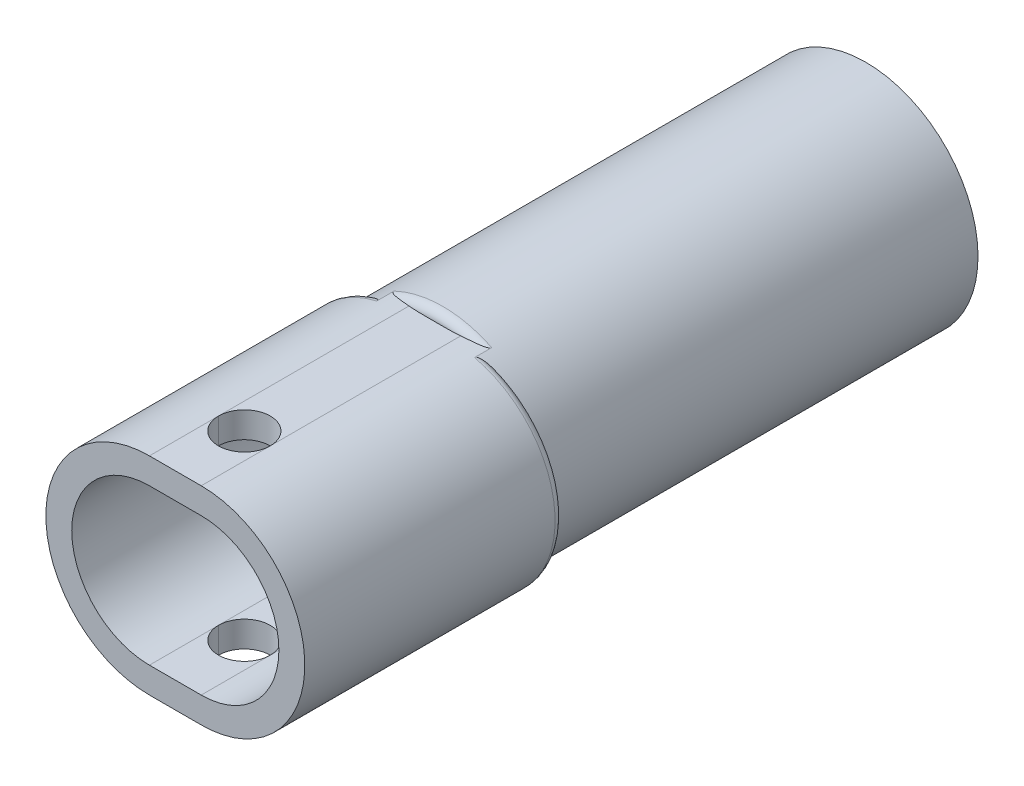
SolidWorks part; units mm, degrees
ref_plane "Front Plane" through (0, 0, 0) normal (0, 0, 1) x (1, 0, 0)
ref_plane "Top Plane" through (0, 0, 0) normal (0, 1, 0) x (1, 0, 0)
ref_plane "Right Plane" through (0, 0, 0) normal (1, 0, 0) x (0, 0, -1)
sketch "Sketch1" plane through (0, 0, 0) normal (0, 0, 1) x (1, 0, 0)
  line L0 (3, 0) -> (-3, 0) construction
  line L1 (3, -9) -> (-3, -9)
  line L2 (3, 9) -> (-3, 9)
  line L3 (-3, 0) -> (3, 0) construction
  line L4 (-3, 12) -> (3, 12)
  line L5 (-3, -12) -> (3, -12)
  arc A1 (3, -9) -> (3, 9) centre (3, 0) ccw
  arc A2 (-3, 9) -> (-3, -9) centre (-3, 0) ccw
  arc A3 (-3, 12) -> (-3, -12) centre (-3, 0) ccw
  arc A4 (3, -12) -> (3, 12) centre (3, 0) ccw
  point P5 (0, 0)
  point P10 (0, 0)
  dimension "D1" = 6
  dimension "D3" = 24
  dimension "D4" = 6
  dimension "D2" = 18
extrude "Boss-Extrude1" add sketch "Sketch1" along normal blind 30
sketch "Sketch2" plane through (0, 0, 0) normal (0, 0, -1) x (-1, 0, 0)
  circle A0 centre (0, 0) radius 13
  dimension "D1" = 26
extrude "Boss-Extrude2" add sketch "Sketch2" along normal blind 50
sketch "Sketch3" plane through (0, 0, -50) normal (0, 0, -1) x (-1, 0, 0)
  circle A0 centre (0, 0) radius 5
  dimension "D1" = 10
extrude "Cut-Extrude1" cut sketch "Sketch3" against normal blind 40
sketch "Sketch4" plane through (0, 12, 0) normal (0, 1, 0) x (1, 0, 0)
  line L0 (3, -30) -> (-3, -30) construction
  circle A0 centre (0, -22) radius 3
  dimension "D1" = 6
  dimension "D2" = 8
extrude "Cut-Extrude2" cut sketch "Sketch4" against normal through all
fillet "Fillet1" radius 1 4 edges at (4.3417, 11.9248, 0) (0, 13, 0) (0, 12, 0) (-4.3417, 11.9248, 0)
fillet "Fillet2" radius 1 2 edges at (-15, 0, 0) (15, 0, 0)
fillet "Fillet3" radius 1 1 edges at (0, -13, 0)
ref_plane "Plane1" through (0, 0, 22) normal (0, 0, -1) x (-1, 0, 0)
sketch "Sketch5" plane through (0, 0, 22) normal (0, 0, -1) x (-1, 0, 0)
  line L0 (3, 12) -> (-3, 12)
ref_plane "Plane2" through (0, 0, 22) normal (0, 0, -1) x (-1, 0, 0)
sketch "Sketch6" plane through (0, 0, 22) normal (0, 0, -1) x (-1, 0, 0)
  line L0 (-3, 9) -> (-3, 12)
  line L1 (-3, 12) -> (3, 12)
  line L2 (3, 12) -> (3, 9)
  line L3 (3, 9) -> (-3, 9)
split line "Split Line2"
ref_plane "Plane3" through (0, 0, 22) normal (0, 0, -1) x (-1, 0, 0)
sketch "Sketch7" plane through (0, 0, 22) normal (0, 0, -1) x (-1, 0, 0)
  line L0 (-3, -9) -> (-3, -12)
  line L1 (-3, -12) -> (3, -12)
  line L2 (3, -12) -> (3, -9)
  line L3 (3, -9) -> (-3, -9)
split line "Split Line3"
